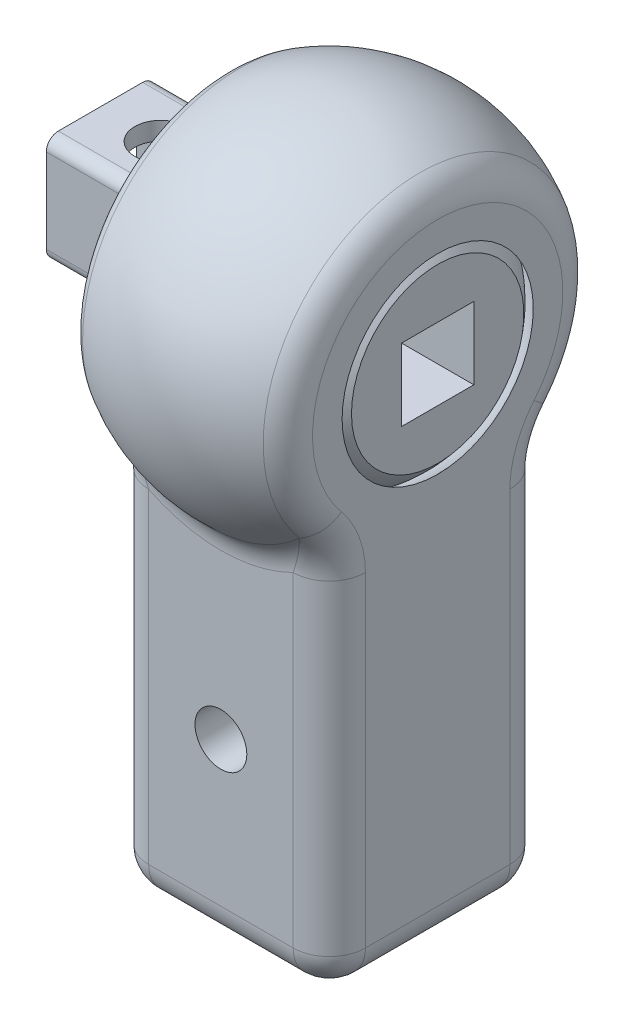
SolidWorks part; units mm, degrees
ref_plane "Alzado" through (0, 0, 0) normal (0, 0, 1) x (1, 0, 0)
ref_plane "Planta" through (0, 0, 0) normal (0, 1, 0) x (1, 0, 0)
ref_plane "Vista lateral" through (0, 0, 0) normal (1, 0, 0) x (0, 0, -1)
sketch "Croquis1" plane through (0, 0, 0) normal (0, 0, 1) x (1, 0, 0)
  line L0 (0, 0) -> (0, 30) construction
  line L1 (0, 27) -> (0, 30)
  line L2 (0, 30.5) -> (0, 42) construction
  line L3 (0, 30.5) -> (0, 53.5)
  line L4 (0, 54) -> (0, 57)
  arc A0 (0, 30.5) -> (0, 53.5) centre (0, 42) ccw
  arc A1 (0, 27) -> (0, 57) centre (0, 42) ccw
  arc A2 (0, 30) -> (0, 54) centre (0, 42) ccw
  dimension "D2" = 23
  dimension "D3" = 30
  dimension "D4" = 12
  dimension "D1" = 42
revolve "Revolución1" add sketch "Croquis1" angle 360 about L0
sketch "Croquis2" plane through (0, 0, 0) normal (0, 0, 1) x (1, 0, 0)
  line L0 (0, 0) -> (0, 42) construction
  line L1 (0, 42) -> (-9, 42) construction
  line L2 (-9, 42) -> (-9, 57)
  line L3 (-9, 57) -> (-19, 57)
  line L4 (-19, 57) -> (-19, 27)
  line L5 (-19, 27) -> (-9, 27)
  line L6 (-9, 27) -> (-9, 42)
  line L7 (-9, 42) -> (-15, 42) construction
  line L8 (19, 27) -> (9, 27)
  line L9 (19, 57) -> (19, 27)
  line L10 (9, 57) -> (19, 57)
  line L11 (9, 42) -> (9, 57)
  line L12 (9, 27) -> (9, 42)
  circle A0 centre (0, 42) radius 15 construction
  dimension "D1" = 42
  dimension "D2" = 6
  dimension "D3" = 30
  dimension "D4" = 10
extrude "Cortar-Extruir1" cut sketch "Croquis2" against normal through all both and the other way through all
sketch "Croquis3" plane through (0, 0, 0) normal (0, 1, 0) x (1, 0, 0)
  line L0 (9, -12) -> (9, 12) construction
  line L1 (-9, -9) -> (9, -9)
  line L2 (-9, -9) -> (-9, 9)
  line L3 (-9, 9) -> (9, 9)
  line L4 (9, -9) -> (9, 9)
  line L5 (-9, -9) -> (9, 9) construction
  line L6 (-9, 9) -> (9, -9) construction
  point P0 (0, 0)
  dimension "D1" = 18
  dimension "D2" = 18
extrude "Saliente-Extruir1" add sketch "Croquis3" along normal up to surface (34.0627 mm away) up to face at (9, 42, 12)
sketch "Croquis4" plane through (-9, 0, 0) normal (-1, 0, 0) x (0, 0, 1)
  line L0 (-7.1589, 42) -> (7.1589, 42) construction
  line L2 (-3, 45) -> (3, 45)
  line L3 (-3, 45) -> (-3, 39)
  line L4 (-3, 39) -> (3, 39)
  line L5 (3, 45) -> (3, 39)
  line L6 (-3, 45) -> (3, 39) construction
  line L7 (-3, 39) -> (3, 45) construction
  circle A1 centre (0, 42) radius 7.1589 construction
  point P4 (0, 42)
  dimension "D1" = 6
  dimension "D2" = 6
extrude "Cortar-Extruir2" cut sketch "Croquis4" against normal through all both and the other way through all
sketch "Croquis5" plane through (-9, 0, 0) normal (-1, 0, 0) x (0, 0, 1)
  line L0 (-3, 42) -> (3, 42) construction
  line L1 (-3, 45) -> (3, 45)
  line L2 (-3, 45) -> (-3, 39)
  line L3 (-3, 39) -> (3, 39)
  line L4 (3, 45) -> (3, 39)
  line L5 (-3, 45) -> (3, 39) construction
  line L6 (-3, 39) -> (3, 45) construction
  line L7 (-3, 39) -> (-3, 45) construction
  line L8 (-4.5, 46.5) -> (4.5, 46.5)
  line L9 (-4.5, 46.5) -> (-4.5, 37.5)
  line L10 (-4.5, 37.5) -> (4.5, 37.5)
  line L11 (4.5, 46.5) -> (4.5, 37.5)
  line L12 (-4.5, 46.5) -> (4.5, 37.5) construction
  line L13 (-4.5, 37.5) -> (4.5, 46.5) construction
  point P0 (0, 42)
  point P10 (0, 42)
  point P16 (0, 42)
  dimension "D1" = 6
  dimension "D2" = 1.5
  dimension "D3" = 1.5
extrude "Saliente-Extruir2" add sketch "Croquis5" along normal blind 10
sketch "Croquis7" plane through (0, 0, 9) normal (0, 0, 1) x (1, 0, 0)
  line L0 (0, 0) -> (0, 15) construction
  circle A0 centre (0, 15) radius 2.15
  dimension "D2" = 4.3
  dimension "D1" = 15
extrude "Cortar-Extruir3" cut sketch "Croquis7" against normal through all both and the other way through all
fillet "Redondeo1" radius 3 12 edges at (-9, 17.0314, 9) (0, 0, 9) (-9, 0, 0) (0, 30, 9) (9, 17.0314, 9) (-9, 54, 0) (-9, 17.0314, -9) (9, 0, 0) (0, 0, -9) (9, 54, 0) (0, 30, -9) (9, 17.0314, -9)
sketch "Croquis8" plane through (0, 46.5, 0) normal (0, 1, 0) x (1, 0, 0)
  line L0 (-19, 0) -> (-9, 0) construction
  line L1 (-19, -4.5) -> (-19, 4.5) construction
  line L2 (-9, -4.5) -> (-9, 4.5) construction
  circle A0 centre (-14, 0) radius 2.15
  dimension "D1" = 4.3
extrude "Cortar-Extruir4" cut sketch "Croquis8" against normal blind 10
fillet "Redondeo2" radius 1 4 edges at (-14, 37.5, 4.5) (-14, 37.5, -4.5) (-14, 46.5, -4.5) (-14, 46.5, 4.5)
fillet "Redondeo3" radius 0.5 8 edges at (-9, 37.7929, -4.2071) (-9, 42, -4.5) (-9, 46.2071, -4.2071) (-9, 46.5, 0) (-9, 46.2071, 4.2071) (-9, 42, 4.5) (-9, 37.7929, 4.2071) (-9, 37.5, 0)
